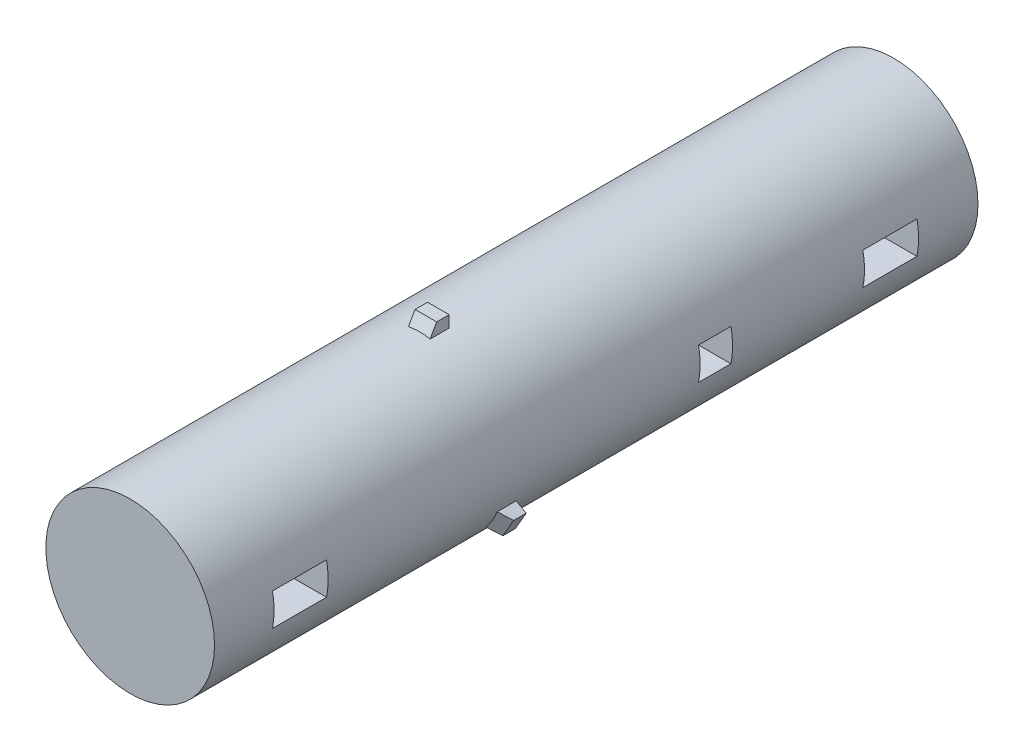
SolidWorks part; units mm, degrees
ref_plane "Front Plane" through (0, 0, 0) normal (0, 0, 1) x (1, 0, 0)
ref_plane "Top Plane" through (0, 0, 0) normal (0, 1, 0) x (1, 0, 0)
ref_plane "Right Plane" through (0, 0, 0) normal (1, 0, 0) x (0, 0, -1)
sketch "Sketch1" plane through (0, 0, 0) normal (0, 0, 1) x (1, 0, 0)
  circle A0 centre (0, 0) radius 3.9
  dimension "D1" = 7.8
extrude "Boss-Extrude1" add sketch "Sketch1" along normal blind 35.3
sketch "Sketch2" plane through (0, 0, 35.3) normal (0, 0, 1) x (1, 0, 0)
  line L0 (3.9, -3.9) -> (-3.9, -3.9)
  line L1 (3.9, -3.9) -> (3.9, 3.9)
  line L2 (-3.9, -3.9) -> (-3.9, 3.9)
  line L3 (3.9, 3.9) -> (-3.9, 3.9)
  line L4 (3.9, -3.9) -> (-3.9, 3.9) construction
  line L5 (-3.9, -3.9) -> (3.9, 3.9) construction
  circle A0 centre (0, 0) radius 3.9 construction
  point P1 (0, 0)
sketch "Sketch3" plane through (0, 0, 0) normal (1, 0, 0) x (0, 0, -1)
  line L0 (-35.3, 0) -> (0, 0)
  line L1 (-32.55, -0.75) -> (-30.05, -0.75)
  line L2 (-32.55, -0.75) -> (-32.55, 0.75)
  line L3 (-32.55, 0.75) -> (-30.05, 0.75)
  line L4 (-30.05, -0.75) -> (-30.05, 0.75)
  line L5 (-32.55, -0.75) -> (-30.05, 0.75) construction
  line L6 (-32.55, 0.75) -> (-30.05, -0.75) construction
  point P0 (-31.3, 0)
  dimension "D1" = 2.5
  dimension "D2" = 1.5
  dimension "D3" = 4
extrude "Cut-Extrude2" cut sketch "Sketch3" against normal through all both and the other way through all contours L1 L4 L0 L2 | L0 L4 L3 L2 region at (0, 0.375, 31.3) region at (0, -0.375, 31.3)
sketch "Sketch5" plane through (0, 0, 0) normal (0, 1, 0) x (1, 0, 0)
  line L0 (0, 0) -> (0, -35.3)
  point P4 (0, -17.65)
ref_plane "Plane2" through (0, 0, 17.65) normal (0, 0, 1) x (1, 0, 0)
mirror "Mirror1" about plane through (0, 0, 17.65) normal (0, 0, 1) of "Cut-Extrude2"
sketch "Sketch6" plane through (0, 0, 0) normal (1, 0, 0) x (0, 0, -1)
  line L0 (0, 3.9) -> (-35.3, 3.9) construction
  line L1 (-22.65, 3.9) -> (-12.65, 3.9)
  line L2 (-22.65, 3.9) -> (-22.65, -3.9)
  line L3 (-22.65, -3.9) -> (-12.65, -3.9)
  line L4 (-12.65, 3.9) -> (-12.65, -3.9)
  line L5 (-35.3, -3.9) -> (0, -3.9) construction
  line L6 (-35.3, 0) -> (0, 0) construction
  line L7 (-17.65, 0) -> (-17.65, 3.9)
  line L8 (-17.65, 4.29) -> (-17.65, -4.29) construction
  line L9 (0, 0) -> (-35.3, 0) construction
  line L10 (-12.85, -0.75) -> (-11.35, -0.75)
  line L11 (-12.85, -0.75) -> (-12.85, 0.75)
  line L12 (-12.85, 0.75) -> (-11.35, 0.75)
  line L13 (-11.35, -0.75) -> (-11.35, 0.75)
  line L14 (-12.85, -0.75) -> (-11.35, 0.75) construction
  line L15 (-12.85, 0.75) -> (-11.35, -0.75) construction
  point P17 (-12.1, 0)
  dimension "D1" = 10
  dimension "D2" = 1.5
  dimension "D3" = 1.5
  dimension "D4" = 0.2
extrude "Cut-Extrude3" cut sketch "Sketch6" against normal through all both and the other way through all contours L13 L12 L11 L10
sketch "Sketch7" plane through (0, 0, 0) normal (1, 0, 0) x (0, 0, -1)
  line L1 (-22.65, -3.9) -> (-12.65, -3.9) construction
  line L2 (-22.65, -3.9) -> (-22.65, 3.9) construction
  line L3 (-22.65, 3.9) -> (-12.65, 3.9) construction
  line L4 (-12.65, -3.9) -> (-12.65, 3.9) construction
  line L5 (-22.65, -3.9) -> (-12.65, 3.9) construction
  line L6 (-22.65, 3.9) -> (-12.65, -3.9) construction
  line L10 (-22.2047, 3.4) -> (-21.6274, 4.4)
  line L11 (-22.2047, 3.4) -> (-21.05, 3.4)
  line L12 (-22.2047, 3.4) -> (-22.2047, 4.4)
  line L13 (-22.2047, 4.4) -> (-21.05, 4.4)
  line L14 (-21.05, 3.4) -> (-21.05, 4.4)
  line L15 (0, 3.9) -> (-35.3, 3.9) construction
  line L16 (-12.85, -0.75) -> (-12.85, 0.75) construction
  point P0 (-17.65, 0)
  dimension "D1" = 10
  dimension "D2" = 8.2
  dimension "D3" = 0.5
  dimension "D4" = 60
  dimension "D5" = 0.5
extrude "Boss-Extrude2" add sketch "Sketch7" along normal mid plane 1 contours L3 L14 L13 L10 L11 L2 | L2 L1 L4 L3 region at (0, 3.8444, 21.4991)
pattern_circular "CirPattern1" count 3 over 360 about axis through (0, 0, 0) along (0, 0, 1) of "Boss-Extrude2" reverse direction yes
